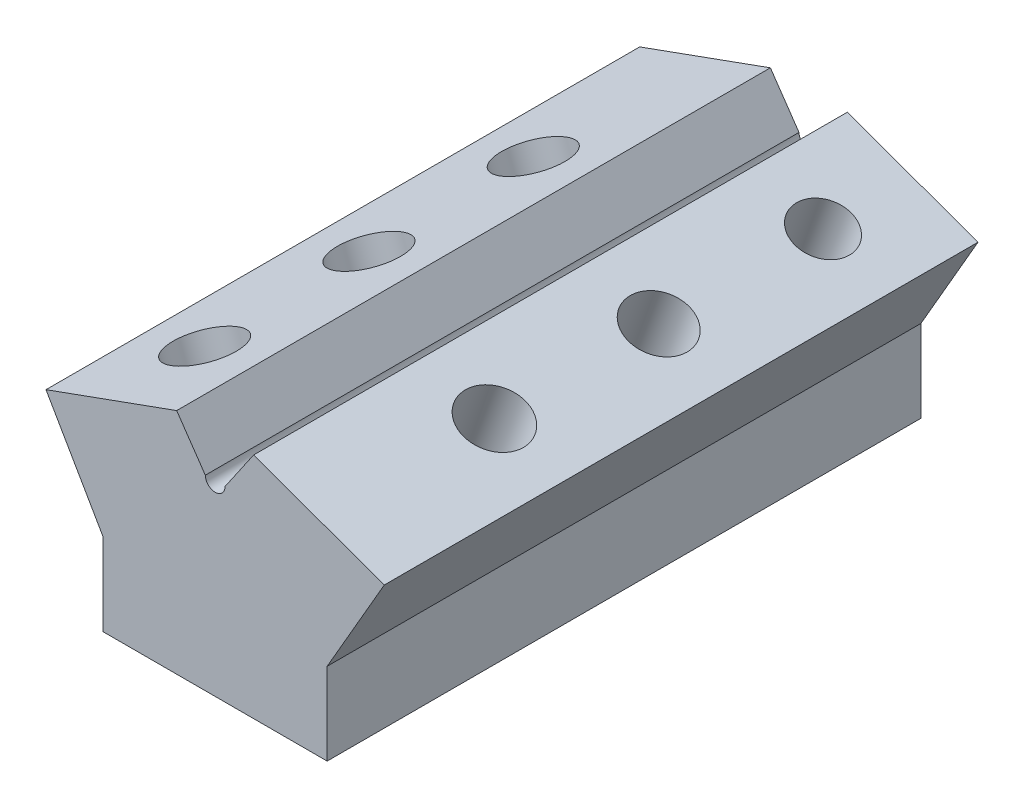
SolidWorks part; units mm, degrees
ref_plane "Front Plane" through (0, 0, 0) normal (0, 0, 1) x (1, 0, 0)
ref_plane "Top Plane" through (0, 0, 0) normal (0, 1, 0) x (1, 0, 0)
ref_plane "Right Plane" through (0, 0, 0) normal (1, 0, 0) x (0, 0, -1)
sketch "Sketch1" plane through (0, 0, 0) normal (0, 0, 1) x (1, 0, 0)
  line L0 (0, 0) -> (120158.4261, 0) construction
  line L1 (0, 0) -> (0, 120158.4261) construction
  line L2 (76.2, 0) -> (76.2, 55.88)
  line L3 (76.2, 55.88) -> (115.0614, 123.19)
  line L4 (115.0614, 123.19) -> (26.1614, 155.3261)
  line L5 (-76.2, 0) -> (76.2, 0)
  line L6 (26.1614, 155.3261) -> (6.6884, 127)
  line L7 (0, 0) -> (-120158.4261, 0) construction
  line L8 (-26.1614, 155.3261) -> (-6.6884, 127)
  line L9 (-115.0614, 123.19) -> (-26.1614, 155.3261)
  line L10 (-76.2, 55.88) -> (-115.0614, 123.19)
  line L11 (-76.2, 0) -> (-76.2, 55.88)
  arc A0 (-6.6884, 127) -> (6.6884, 127) centre (0, 127) ccw
  point P17 (0, 0)
  dimension "D1" = 76.2
  dimension "D2" = 55.88
  dimension "D3" = 123.19
  dimension "D4" = 60
  dimension "D5" = 88.9
extrude "Boss-Extrude1" add sketch "Sketch1" along normal blind 403.86
sketch "Sketch2" plane through (0, 0, 0) normal (0, 1, 0) x (1, 0, 0)
extrude "Boss-Extrude2" add sketch "Sketch1<2>" along normal blind 403.86
sketch "Sketch1<2>" plane through (0, 0, 0) normal (0, 0, 1) x (1, 0, 0) same geometry as "Sketch1"
sketch "Sketch3" plane through (52.6827, 145.7391, 0) normal (0.34, 0.9404, 0) x (0.9404, -0.34, 0)
  line L0 (66.3293, 0) -> (-28.2008, 0) construction
  line L1 (66.3293, -403.86) -> (-28.2008, -403.86) construction
  line L2 (-28.2008, -403.86) -> (-28.2008, 0) construction
  line L3 (66.3293, -403.86) -> (66.3293, 0) construction
  circle A0 centre (19.0432, -60.96) radius 19.0916
  circle A1 centre (19.0432, -172.72) radius 20.57
  circle A2 centre (19.0432, -284.48) radius 20.9844
  dimension "D1" = 60.96
  dimension "D2" = 111.76
  dimension "D3" = 111.76
  dimension "D4" = 119.38
  dimension "D5" = 94.5301
  dimension "D6" = 47.244
extrude "Cut-Extrude2" cut sketch "Sketch3" against normal through all from offset 19.05
sketch "Sketch4" plane through (-52.6827, 145.7391, 0) normal (-0.34, 0.9404, 0) x (0.9404, 0.34, 0)
  line L0 (-66.3293, -403.86) -> (-66.3293, 0) construction
  line L1 (28.2008, -403.86) -> (-66.3293, -403.86) construction
  circle A0 centre (-19.0853, -116.84) radius 22.86
  circle A1 centre (-19.0853, -228.6) radius 22.86
  circle A2 centre (-19.0853, -340.36) radius 22.86
  point P10 (-19.0642, -403.86)
  dimension "D1" = 45.72
  dimension "D2" = 45.72
  dimension "D3" = 45.72
  dimension "D4" = 47.244
  dimension "D5" = 47.244
  dimension "D6" = 47.244
  dimension "D7" = 63.5
  dimension "D8" = 111.76
  dimension "D9" = 111.76
extrude "Cut-Extrude3" cut sketch "Sketch4" against normal through all from offset 19.05
sketch "Sketch6" plane through (0, 0, 0) normal (0, 0, 1) x (1, 0, 0)
  line L0 (-76.2, 0) -> (76.2, 0) construction
  line L1 (50.8113, 0) -> (-50.8113, 0)
  line L2 (50.8113, 0) -> (50.8113, 31.75)
  line L4 (-50.8113, 0) -> (-50.8113, 31.75)
  line L5 (0, 0) -> (0, 50000) construction
  line L6 (-50.8113, 31.75) -> (-26.3024, 45.8193)
  line L7 (50.8113, 31.75) -> (26.3024, 45.8193)
  arc A0 (26.3024, 45.8193) -> (-26.3024, 45.8193) centre (0, 0) ccw
  dimension "D3" = 105.664
  dimension "D1" = 31.75
  dimension "D2" = 101.6226
extrude "Cut-Extrude4" cut sketch "Sketch6" along normal blind 353.06 from offset 25.4
sketch "Sketch7" plane through (0, 0, 0) normal (0, -1, 0) x (1, 0, 0)
  line L0 (-76.2, 403.86) -> (76.2, 403.86) construction
  line L1 (-76.2, 403.86) -> (-76.2, 0) construction
  line L2 (-50.8113, 378.46) -> (50.8113, 378.46) construction
  line L3 (76.2, 403.86) -> (76.2, 0) construction
  line L4 (-76.2, 0) -> (76.2, 0) construction
  line L5 (50.8113, 25.4) -> (26.3024, 25.4) construction
  circle A0 centre (-63.5, 391.16) radius 6.35
  circle A1 centre (63.5, 12.7) radius 6.35
  dimension "D1" = 12.7
  dimension "D5" = 12.7
  dimension "D6" = 12.7
  dimension "D2" = 12.7
  dimension "D3" = 12.7
  dimension "D4" = 12.7
  dimension "D7" = 12.7
  dimension "D8" = 12.7
extrude "Cut-Extrude8" cut sketch "Sketch7" against normal blind 76.2
sketch "Sketch5" plane through (0, 0, 403.86) normal (0, 0, 1) x (1, 0, 0)
  line L0 (-76.2, 0) -> (76.2, 0) construction
  line L1 (-50.8886, 0) -> (50.7351, 0)
  line L2 (-50.8886, 0) -> (-50.8886, 31.75)
  line L4 (50.7351, 0) -> (50.7351, 31.75)
  line L5 (0, 0) -> (0, 50000) construction
  line L6 (-50.8886, 31.75) -> (-22.1953, 47.9436)
  line L7 (21.843, 48.1052) -> (50.7351, 31.75)
  arc A0 (30.0042, 43.4852) -> (-29.5712, 43.7809) centre (0, 0) ccw
  dimension "D3" = 105.664
  dimension "D1" = 101.6237
  dimension "D2" = 31.75
